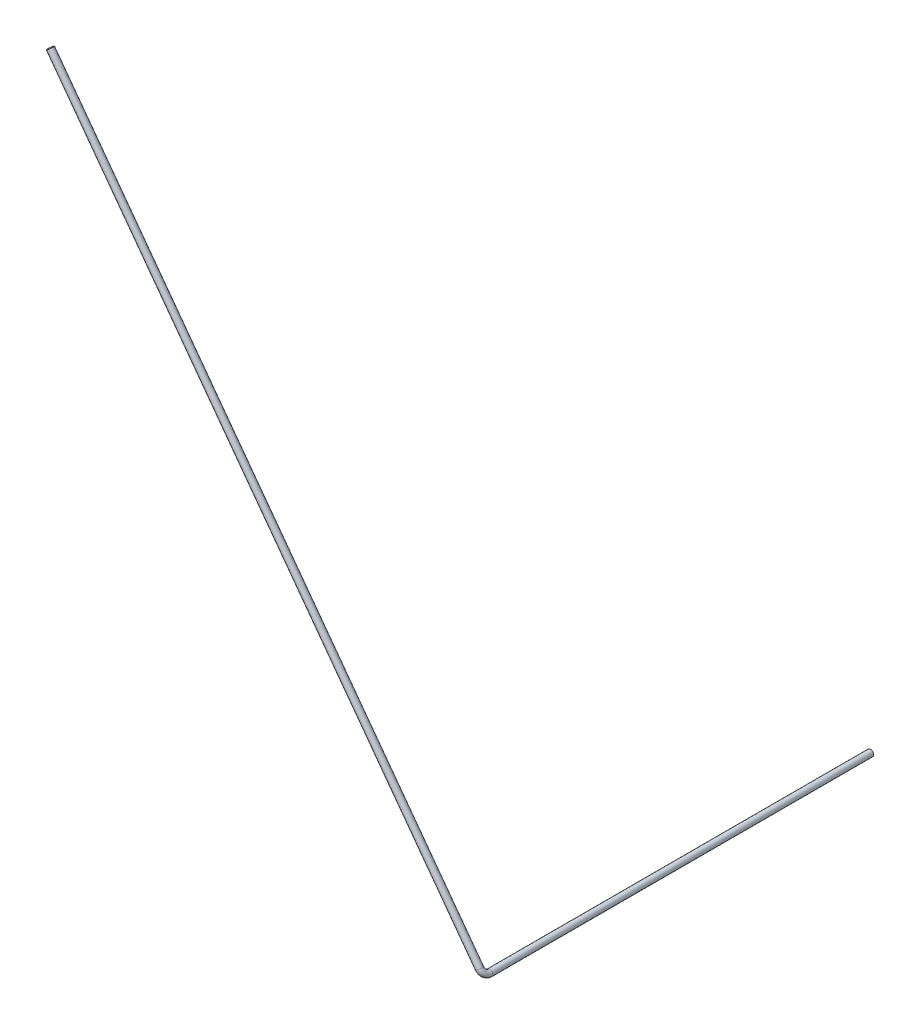
SolidWorks part; units mm, degrees
ref_plane "Plano frontal" through (0, 0, 0) normal (0, 0, 1) x (1, 0, 0)
ref_plane "Plano superior" through (0, 0, 0) normal (0, 1, 0) x (1, 0, 0)
ref_plane "Plano direito" through (0, 0, 0) normal (1, 0, 0) x (0, 0, -1)
sketch3d "3DSketch2"
  line L0 (-33115.197, -14066.9803, 42985.8247) -> (-33115.197, -14066.9803, 43010.9557) construction
  line L1 (-33089.0505, -14047.955, 43030.726) -> (-33089.0505, -14047.955, 42966.0544) construction
  line L2 (-33099.2108, -14055.3481, 43030.726) -> (-33078.8901, -14040.5619, 43030.726) construction
  line L3 (-31046.0335, -16820.5926, 41171.2115) -> (-31046.0335, -16820.5926, 42968.3902)
  line L4 (-31046.0335, -16257.8595, 41013.2907) -> (-31046.0335, -16257.8595, 41171.2115) construction
  line L5 (-31046.0335, -16257.8595, 41013.2907) -> (-31046.0335, -16257.8595, 40878.7861) construction
  line L6 (-33078.8901, -14040.5619, 42966.0544) -> (-33099.2108, -14055.3481, 42966.0544) construction
  line L7 (-33115.197, -14066.9803, 42998.3902) -> (-33062.904, -14028.9296, 42998.3902) construction
  line L8 (-31046.0335, -16257.8595, 41171.2115) -> (-31046.0335, -16881.057, 41171.2115) construction
  line L9 (-33062.904, -14028.9296, 43010.9557) -> (-33062.904, -14028.9296, 42985.8247) construction
  line L10 (-31046.0335, -16820.5926, 42998.3902) -> (-31046.0335, -14851.7592, 42998.3902) construction
  line L11 (-33126.1177, -13997.0136, 42925.3902) -> (-33126.1177, -13997.0136, 42998.3902) construction
  line L12 (-33126.1177, -13997.0136, 42998.3902) -> (-33088.7507, -14047.7369, 42998.3902) construction
  line L13 (-31063.827, -16796.4391, 42998.3902) -> (-33088.7507, -14047.7369, 42998.3902)
  line L14 (-31046.0335, -14851.7592, 42998.3902) -> (-32496.4407, -14851.7592, 42998.3902) construction
  arc A0 (-31046.0335, -16820.5926, 42968.3902) -> (-31063.827, -16796.4391, 42998.3902) centre (-31063.827, -16796.4391, 42968.3902) ccw
  point P18 (0, 0, 0)
  point P19 (0, 0, 0)
  point P27 (0, 0, 0)
  point P30 (-31046.0335, -16820.5926, 42998.3902)
  point P32 (-31087.9805, -16814.2326, 42968.3902)
  dimension "D1" = 30
sweep "Sweep-Thin1" add path "3DSketch2" circular profile diameter 30 parameters "D1"=1, "D3"=30
